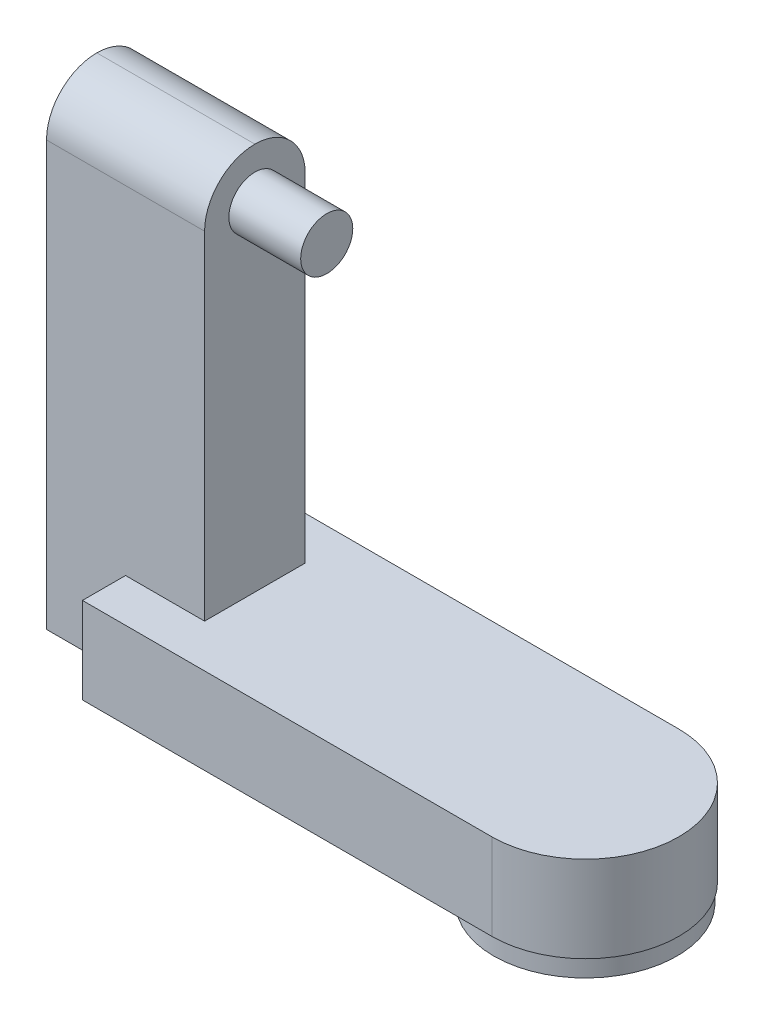
SolidWorks part; units mm, degrees
ref_plane "Front Plane" through (0, 0, 0) normal (0, 0, 1) x (1, 0, 0)
ref_plane "Top Plane" through (0, 0, 0) normal (0, 1, 0) x (1, 0, 0)
ref_plane "Right Plane" through (0, 0, 0) normal (1, 0, 0) x (0, 0, -1)
sketch "Sketch1" plane through (0, 0, 0) normal (0, 1, 0) x (1, 0, 0)
  line L1 (-114, 26) -> (0, 26)
  line L2 (-114, 26) -> (-114, -26)
  line L3 (-114, -26) -> (0, -26)
  arc A1 (0, -26) -> (0, 26) centre (0, 0) ccw
  point P3 (-46.1648, 0.8875)
  dimension "D3" = 114
  dimension "D2" = 52
extrude "Boss-Extrude2" add sketch "Sketch1" along normal blind 24
sketch "Sketch2" plane through (0, 0, 0) normal (0, -1, 0) x (1, 0, 0)
  circle A0 centre (0, 0) radius 25.5
extrude "Boss-Extrude3" add sketch "Sketch2" along normal blind 5
sketch "Sketch3" plane through (0, 0, 0) normal (0, 1, 0) x (1, 0, 0)
  line L0 (-114, 26) -> (-114, -26) construction
  line L1 (-136, 14) -> (-92, 14)
  line L2 (-136, 14) -> (-136, -14)
  line L3 (-136, -14) -> (-92, -14)
  line L4 (-92, 14) -> (-92, -14)
  line L5 (-136, 14) -> (-92, -14) construction
  line L6 (-136, -14) -> (-92, 14) construction
  point P0 (-114, 0)
  dimension "D1" = 44
  dimension "D2" = 28
extrude "Boss-Extrude4" add sketch "Sketch3" along normal blind 132
fillet "Fillet2" radius 14 1 edges at (-114, 132, 14) type face fillet first side face at (-114, 132, 0) second side face at (-114, 52, 14)
fillet "Fillet5" radius 14 1 edges at (-114, 132, -14) type face fillet first side face at (-114, 132, -7) second side face at (-114, 52, -14)
ref_plane "Plane1" through (-92, 0, 0) normal (1, 0, 0) x (0, 0, -1)
sketch "Sketch4" plane through (-92, 0, 0) normal (1, 0, 0) x (0, 0, -1)
  circle A0 centre (0, 118) radius 7.25
extrude "Boss-Extrude5" add sketch "Sketch4" along normal blind 20
ref_point "Point1"
ref_point "Point2"
ref_axis "Axis1" through (0, 24, 0) along (0, -1, 0)
sketch "Sketch5" plane through (0, -5, 0) normal (0, -1, 0) x (1, 0, 0)
  line L0 (0, 0) -> (0, 25.5) construction
  circle A0 centre (0, 0) radius 25.5 construction
